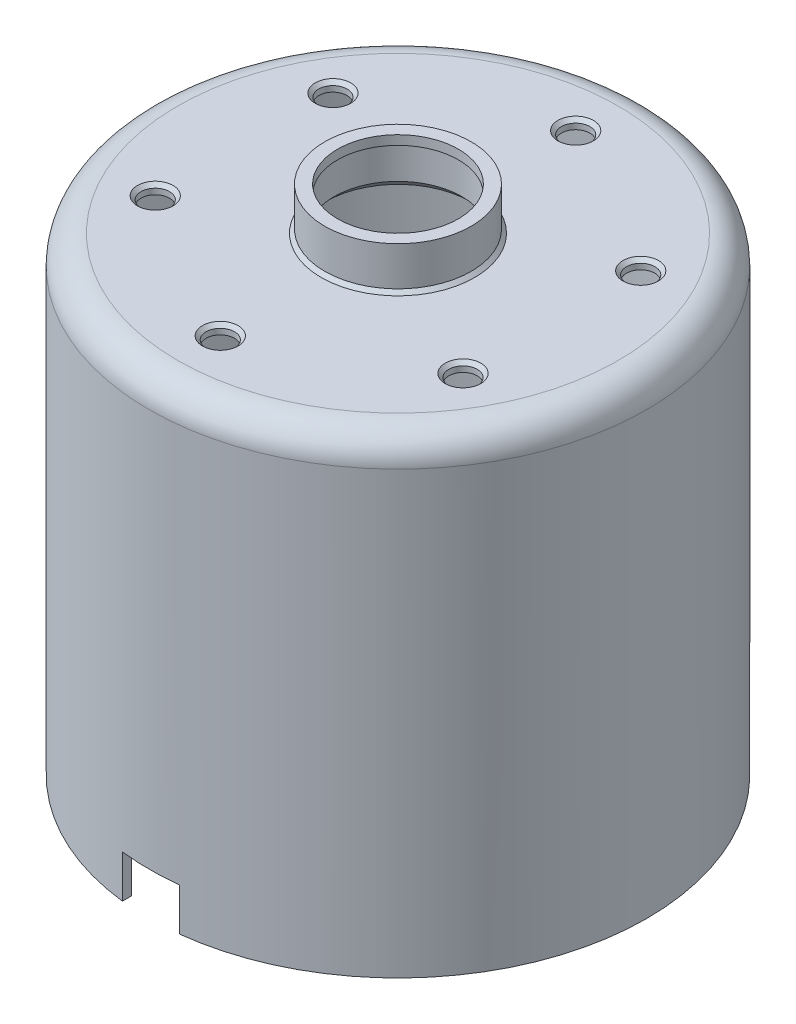
SolidWorks part; units mm, degrees
material "Free-Cutting Brass, UNS C36000"
ref_plane "Front" through (0, 0, 0) normal (0, 0, 1) x (1, 0, 0)
ref_plane "Top" through (0, 0, 0) normal (0, 1, 0) x (1, 0, 0)
ref_plane "Right" through (0, 0, 0) normal (1, 0, 0) x (0, 0, -1)
sketch "Sketch1" plane through (0, 0, 0) normal (0, 1, 0) x (1, 0, 0)
  circle A0 centre (0, 0) radius 17.5
  dimension "D1" = 35
extrude "Boss-Extrude1" add sketch "Sketch1" along normal blind 33
fillet "Fillet1" radius 2 1 edges at (0, 33, 17.5)
sketch "Sketch3" plane through (0, 33, 0) normal (0, 1, 0) x (1, 0, 0)
  circle A0 centre (0, 0) radius 5.15
  dimension "D1" = 10.3
extrude "Boss-Extrude2" add sketch "Sketch3" along normal blind 3
sketch "Sketch4" plane through (0, 36, 0) normal (0, 1, 0) x (1, 0, 0)
  circle A0 centre (0, 0) radius 4.25
  dimension "D1" = 8.5
chamfer "Chamfer1" distance 0.25 angle 45 1 edges at (0, 33, 5.15)
shell "Shell1" thickness 0.65 removed face at (0, 0, 17.5)
extrude "Cut-Extrude1" cut sketch "Sketch4" against normal up to next
sketch "Sketch5" plane through (0, 33, 0) normal (0, 1, 0) x (1, 0, 0)
  circle A0 centre (0, 12.5) radius 1
  point P2 (0, 0)
  dimension "D2" = 2
  dimension "D1" = 12.5
extrude "Cut-Extrude2" cut sketch "Sketch5" against normal up to next
chamfer "Chamfer2" distance 0.25 angle 45 1 edges at (0, 33, -11.5)
pattern_circular "CirPattern1" count 6 over 360 about axis through (0, 36, 0) along (0, 1, 0) of "Cut-Extrude2", "Chamfer2"
ref_plane "Plane1" through (0, 0, 17.5) normal (0, 0, 1) x (1, 0, 0)
sketch "Sketch6" plane through (0, 0, 17.5) normal (0, 0, 1) x (1, 0, 0)
  line L0 (-17.5, 0) -> (17.5, 0) construction
  line L1 (-2, -3) -> (2, -3)
  line L2 (-2, -3) -> (-2, 3)
  line L3 (-2, 3) -> (2, 3)
  line L4 (2, -3) -> (2, 3)
  line L5 (-2, -3) -> (2, 3) construction
  line L6 (-2, 3) -> (2, -3) construction
  point P0 (0, 0)
  dimension "D1" = 4
  dimension "D2" = 3
extrude "Cut-Extrude3" cut sketch "Sketch6" against normal up to next
